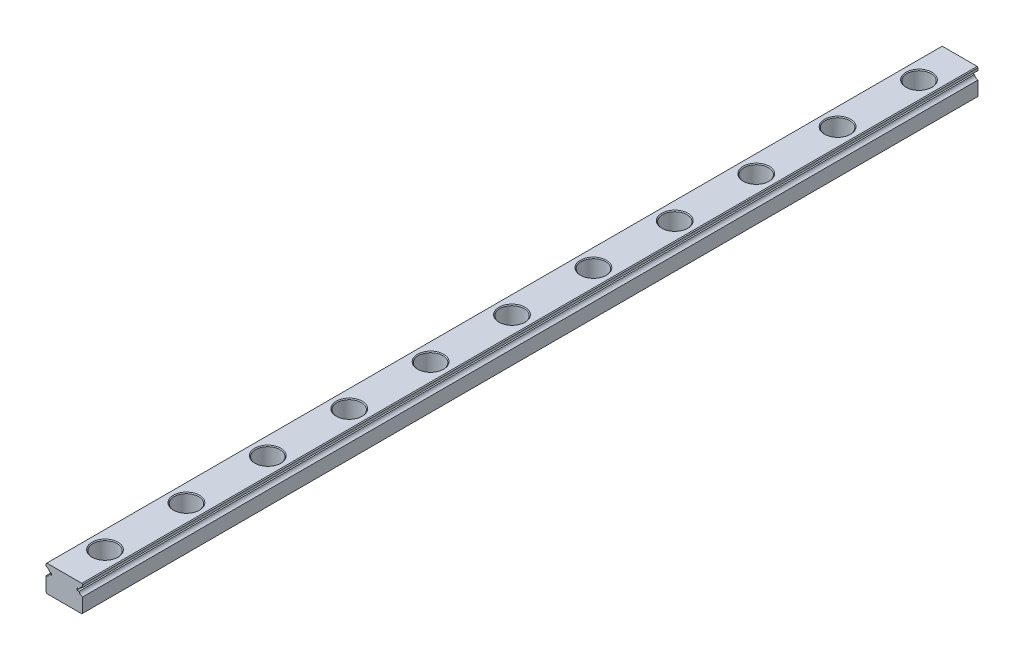
SolidWorks part; units mm, degrees
material "AISI 1035 鋼 (SS)"
ref_plane "Спереди" through (0, 0, 0) normal (0, 0, 1) x (1, 0, 0)
ref_plane "Сверху" through (0, 0, 0) normal (0, 1, 0) x (1, 0, 0)
ref_plane "Справа" through (0, 0, 0) normal (1, 0, 0) x (0, 0, -1)
sketch "Sketch1" plane through (0, 0, 0) normal (0, 0, 1) x (1, 0, 0)
  line L0 (0, 0) -> (0, 4.3706) construction
  line L1 (-4.3, -3.25) -> (4.3, -3.25)
  line L2 (-4.5, -3.05) -> (-4.5, 0.455)
  line L3 (-4.3, 3.25) -> (4.3, 3.25)
  line L4 (4.5, -3.05) -> (4.5, 0.455)
  line L5 (-4.5, -3.25) -> (4.5, 3.25) construction
  line L6 (-4.5, 3.25) -> (4.5, -3.25) construction
  line L7 (-4.5, 2.445) -> (-4.5, 3.05)
  line L8 (4.5, 2.445) -> (4.5, 3.05)
  line L9 (-4.5, -3.05) -> (-4.3, -3.25)
  line L10 (4.3, -3.25) -> (4.5, -3.05)
  line L11 (4.3, 3.25) -> (4.5, 3.05)
  line L12 (-4.5, 3.05) -> (-4.3, 3.25)
  line L13 (3.6318, 1.2) -> (3.1318, 1.2)
  line L14 (-3.6318, 1.2) -> (-3.1318, 1.2)
  line L15 (3.1318, 1.2) -> (3.1318, 1.7)
  line L16 (-3.6318, 1.7) -> (-3.1318, 1.7)
  line L17 (-3.1318, 1.2) -> (-3.1318, 1.7)
  line L18 (3.6318, 1.7) -> (3.1318, 1.7)
  arc A0 (-4.5, 2.445) -> (-3.6318, 1.7) centre (-4.6, 1.45) cw
  arc A1 (4.5, 2.445) -> (3.6318, 1.7) centre (4.6, 1.45) ccw
  arc A2 (-3.6318, 1.2) -> (-4.5, 0.455) centre (-4.6, 1.45) cw
  arc A3 (3.6318, 1.2) -> (4.5, 0.455) centre (4.6, 1.45) ccw
  point P0 (0, 0)
  dimension "D4" = 1
  dimension "D5" = 0.1
  dimension "D1" = 9
  dimension "D2" = 6.5
  dimension "D3" = 1.8
  dimension "D6" = 0.5
  dimension "D7" = 0.5
extrude "Extrude1" add sketch "Sketch1" along normal blind 220
hole_wizard "M3 平盤頭機械螺釘的柱孔1" positions "草圖1" profile "草圖2" counterbore size "M3" standard "Ansi Metric" end condition through all
sketch "草圖1" plane through (0, 3.25, 0) normal (0, 1, 0) x (1, 0, 0)
  line L0 (0, 0) -> (0, -10) construction
  line L1 (4.3, 0) -> (-4.3, 0) construction
  point P0 (0, -10)
  dimension "D1" = 10
sketch "草圖2" plane through (0, 3.25, 10) normal (1, 0, 0) x (0, 0, 1)
  line L0 (0, 0) -> (0, 6.5)
  line L1 (0, 6.5) -> (1.75, 6.5)
  line L3 (1.75, 6.5) -> (1.75, 4.5)
  line L4 (1.75, 4.5) -> (3, 4.5)
  line L5 (3, 4.5) -> (3, 0)
  line L7 (3, 0) -> (0, 0)
  line L11 (0, -6.35) -> (0, 107.95) construction
  dimension "砮 ふ 畖" = 3.5
  dimension "砮 ふ瞏 " = 6.5
  dimension "琖ふ 畖" = 6
  dimension "琖ふ瞏 " = 4.5
chamfer "導角1" distance 0.2 angle 45 2 edges at (0, -3.25, 11.75) (0, 3.25, 13)
pattern_linear "直線複製排列1" count 11 spacing 20 along (0, 0, 1) of "導角1", "M3 平盤頭機械螺釘的柱孔1"
